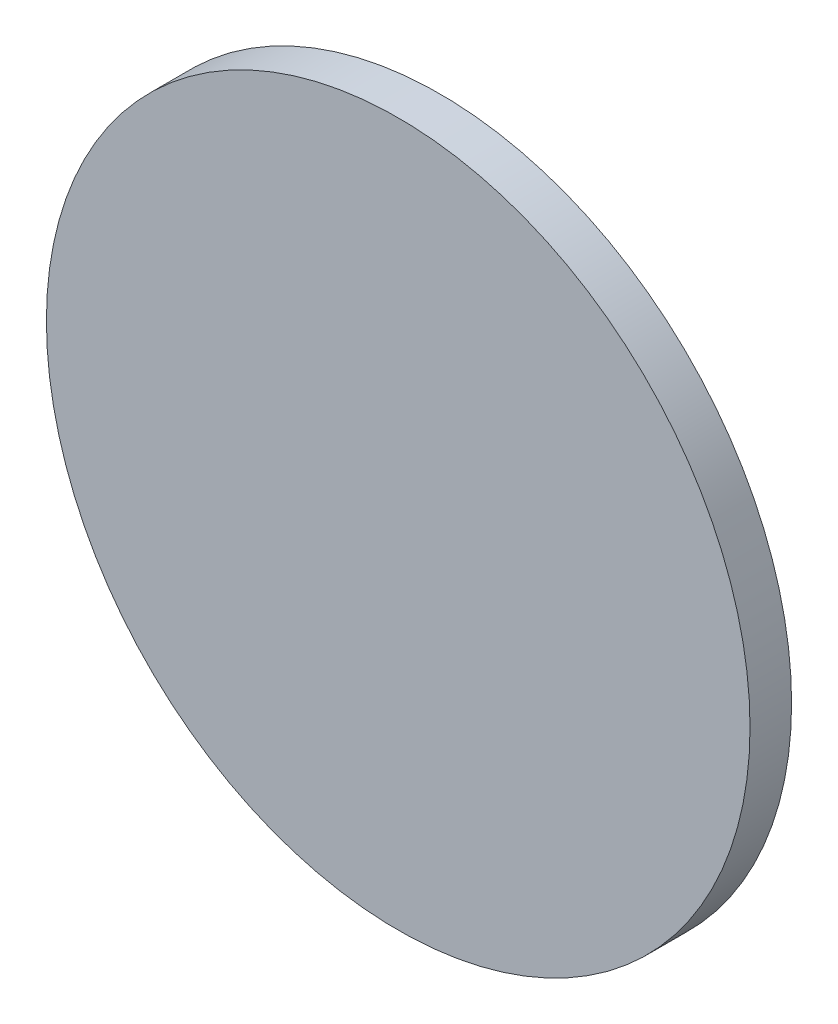
SolidWorks part; units mm, degrees
material "Acrylic (Medium-high impact)"
ref_plane "Front Plane" through (0, 0, 0) normal (0, 0, 1) x (1, 0, 0)
ref_plane "Top Plane" through (0, 0, 0) normal (0, 1, 0) x (1, 0, 0)
ref_plane "Right Plane" through (0, 0, 0) normal (1, 0, 0) x (0, 0, -1)
sketch "Sketch2" plane through (0, 0, 0) normal (0, 0, 1) x (1, 0, 0)
  circle A1 centre (0, 0) radius 25.4
  circle A2 centre (0, 0) radius 25.4
  dimension "D1" = 0
extrude "Boss-Extrude1" add sketch "Sketch2" along normal blind 3
